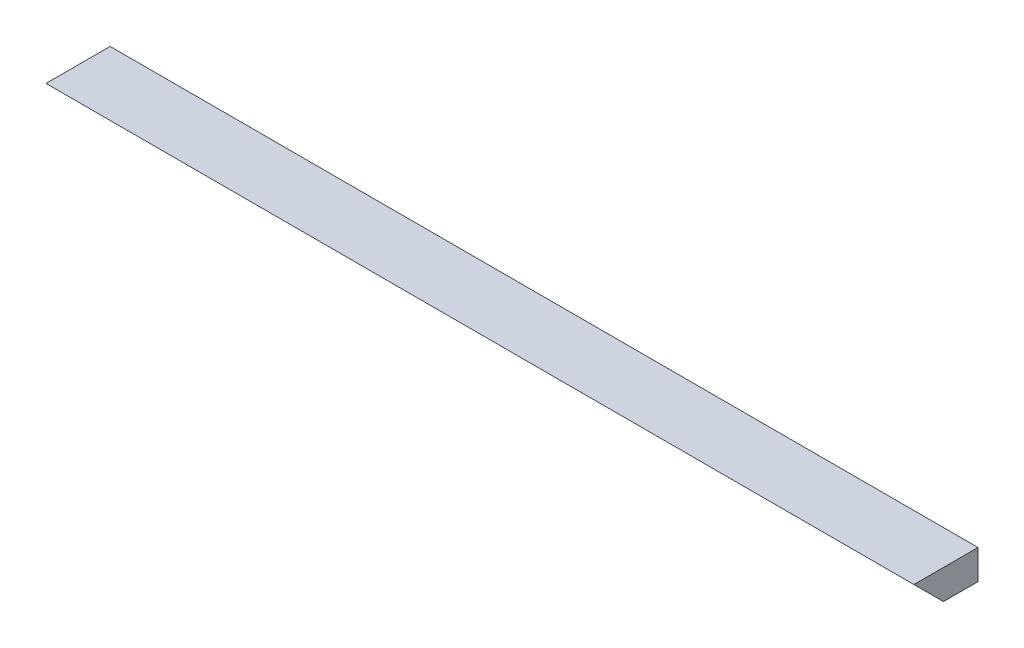
SolidWorks part; units mm, degrees
ref_plane "Front Plane" through (0, 0, 0) normal (0, 0, 1) x (1, 0, 0)
ref_plane "Top Plane" through (0, 0, 0) normal (0, 1, 0) x (1, 0, 0)
ref_plane "Right Plane" through (0, 0, 0) normal (1, 0, 0) x (0, 0, -1)
sketch "Sketch1" plane through (0, 0, 0) normal (1, 0, 0) x (0, 0, -1)
  line L1 (-31.75, -9.525) -> (31.75, -9.525)
  line L2 (-31.75, -9.525) -> (-31.75, 9.525)
  line L3 (-31.75, 9.525) -> (31.75, 9.525)
  line L4 (31.75, -9.525) -> (31.75, 9.525)
  line L5 (-31.75, -9.525) -> (31.75, 9.525) construction
  line L6 (-31.75, 9.525) -> (31.75, -9.525) construction
  point P0 (0, 0)
  dimension "D1" = 63.5
  dimension "D2" = 19.05
extrude "Boss-Extrude1" add sketch "Sketch1" along normal mid plane 558.8
sketch "Sketch2" plane through (0, 0, 0) normal (1, 0, 0) x (0, 0, -1)
  line L0 (-9.525, 9.525) -> (9.525, -9.525)
  line L1 (31.75, 9.525) -> (-31.75, 9.525) construction
  line L2 (-31.75, -9.525) -> (31.75, -9.525) construction
  dimension "D1" = 45
extrude "Cut-Extrude1" cut sketch "Sketch2" against normal through all and the other way through all flip side to cut
